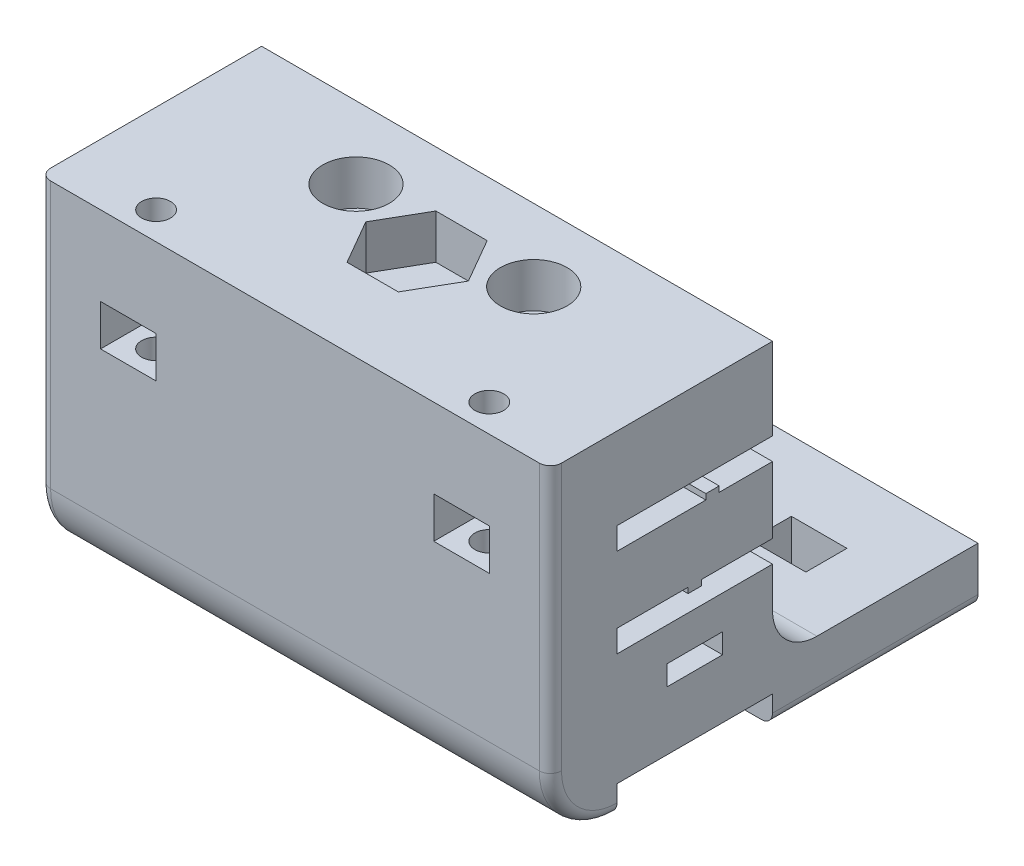
SolidWorks part; units mm, degrees
material "1060 Сплав"
ref_plane "Front" through (0, 0, 0) normal (0, 0, 1) x (1, 0, 0)
ref_plane "Top" through (0, 0, 0) normal (0, 1, 0) x (1, 0, 0)
ref_plane "Right" through (0, 0, 0) normal (1, 0, 0) x (0, 0, -1)
sketch "Эскиз1" plane through (0, 0, 0) normal (0, 0, 1) x (1, 0, 0)
  line L1 (-23, -15) -> (23, -15)
  line L2 (-23, -15) -> (-23, 15)
  line L3 (-23, 15) -> (23, 15)
  line L4 (23, -15) -> (23, 15)
  line L5 (-23, -15) -> (23, 15) construction
  line L6 (-23, 15) -> (23, -15) construction
  point P0 (0, 0)
  dimension "D1" = 30
  dimension "D2" = 46
extrude "Бобышка-Вытянуть1" add sketch "Эскиз1" along normal blind 5
sketch "Эскиз2" plane through (0, 0, 0) normal (0, 0, -1) x (-1, 0, 0)
  line L0 (23, 15) -> (23, -15) construction
  line L1 (-23, -15) -> (23, -15)
  line L2 (-23, -15) -> (-23, -10)
  line L3 (-23, -10) -> (23, -10)
  line L4 (23, -15) -> (23, -10)
  dimension "D1" = 5
extrude "Бобышка-Вытянуть2" add sketch "Эскиз2" along normal blind 33.5
sketch "Эскиз4" plane through (0, 15, 0) normal (0, 1, 0) x (1, 0, 0)
  line L0 (23, -2.5) -> (-23, -2.5) construction
  line L1 (23, -5) -> (23, 0) construction
  line L2 (-23, -5) -> (-23, 0) construction
  circle A0 centre (15, -2.5) radius 1.3
  circle A1 centre (-15, -2.5) radius 1.3
  point P10 (0, -2.5)
  dimension "D1" = 15
  dimension "D2" = 15
extrude "Вырез-Вытянуть2" cut sketch "Эскиз4" against normal blind 15
sketch "Эскиз5" plane through (0, 0, -33.5) normal (0, 0, -1) x (-1, 0, 0)
  line L0 (-23, -12.5) -> (23, -12.5) construction
  line L1 (-23, -10) -> (-23, -15) construction
  line L2 (23, -15) -> (23, -10) construction
  circle A0 centre (-20, -12.5) radius 1.3
  circle A1 centre (20, -12.5) radius 1.3
  point P10 (0, -12.5)
  dimension "D1" = 20
  dimension "D2" = 20
extrude "Вырез-Вытянуть3" cut sketch "Эскиз5" against normal blind 15
sketch "Эскиз6" plane through (0, -10, 0) normal (0, 1, 0) x (1, 0, 0)
  line L0 (-23, 23.5) -> (23, 23.5) construction
  line L1 (-23, 33.5) -> (-23, 0) construction
  line L2 (23, 33.5) -> (23, 0) construction
  line L3 (-23, 33.5) -> (23, 33.5) construction
  line L5 (-17.5, 23.5) -> (-12.5, 23.5)
  line L6 (-17.5, 23.5) -> (-17.5, 27.2)
  line L7 (-17.5, 27.2) -> (-12.5, 27.2)
  line L8 (-12.5, 23.5) -> (-12.5, 27.2)
  line L9 (12.5, 23.5) -> (17.5, 23.5)
  line L10 (12.5, 23.5) -> (12.5, 27.2)
  line L11 (12.5, 27.2) -> (17.5, 27.2)
  line L12 (17.5, 23.5) -> (17.5, 27.2)
  point P16 (0, 23.5)
  dimension "D1" = 10
  dimension "D2" = 3.7
  dimension "D3" = 5
  dimension "D4" = 3.7
  dimension "D5" = 5
  dimension "D6" = 12.5
  dimension "D7" = 12.5
extrude "Вырез-Вытянуть4" cut sketch "Эскиз6" against normal up to next
sketch "Эскиз7" plane through (0, 0, 0) normal (0, 0, -1) x (-1, 0, 0)
  line L1 (23, 15) -> (-23, 15)
  line L2 (23, 15) -> (23, -10)
  line L3 (23, -10) -> (-23, -10)
  line L4 (-23, 15) -> (-23, -10)
extrude "Бобышка-Вытянуть3" add sketch "Эскиз7" along normal blind 15
sketch "Эскиз8" plane through (0, 0, -15) normal (0, 0, -1) x (-1, 0, 0)
  line L0 (-23, 7.62) -> (23, 7.62)
  line L1 (23, -10) -> (23, 15) construction
  line L2 (-23, 15) -> (-23, -10) construction
  line L3 (-23, 5.62) -> (-23, 7.62)
  line L5 (23, 5.62) -> (-23, 5.62)
  line L6 (-23, -2.38) -> (-23, -0.38)
  line L7 (23, 5.62) -> (23, 7.62)
  line L8 (23, -2.38) -> (-23, -2.38)
  line L9 (23, -2.38) -> (23, -0.38)
  line L10 (-23, -0.38) -> (23, -0.38)
  dimension "D2" = 2
extrude "Вырез-Вытянуть5" cut sketch "Эскиз8" against normal blind 14
sketch "Эскиз10" plane through (0, 0, 5) normal (0, 0, 1) x (1, 0, 0)
  line L0 (0, 15) -> (0, -15) construction
  line L1 (23, 15) -> (-23, 15) construction
  line L2 (-23, -15) -> (23, -15) construction
  line L3 (0, 6) -> (15, 6) construction
  line L4 (-17.5, 7.85) -> (-12.5, 4.15) construction
  line L5 (17.5, 4.15) -> (12.5, 4.15)
  line L6 (17.5, 4.15) -> (17.5, 7.85)
  line L7 (17.5, 7.85) -> (12.5, 7.85)
  line L8 (12.5, 4.15) -> (12.5, 7.85)
  line L9 (17.5, 4.15) -> (12.5, 7.85) construction
  line L10 (17.5, 7.85) -> (12.5, 4.15) construction
  line L11 (-17.5, 4.15) -> (-12.5, 7.85) construction
  line L12 (-12.5, 4.15) -> (-12.5, 7.85)
  line L13 (-17.5, 7.85) -> (-12.5, 7.85)
  line L14 (-17.5, 4.15) -> (-17.5, 7.85)
  line L15 (-17.5, 4.15) -> (-12.5, 4.15)
  dimension "D1" = 15
  dimension "D2" = 5
  dimension "D3" = 3.7
  dimension "D4" = 9
extrude "Вырез-Вытянуть7" cut sketch "Эскиз10" against normal blind 5
fillet "Скругление1" radius 6 1 edges at (0, -15, 5)
fillet "Скругление2" radius 4 1 edges at (0, -10, -15)
sketch "Эскиз11" plane through (0, 0, -15) normal (0, 0, -1) x (-1, 0, 0)
  line L0 (-23, 5.62) -> (23, 5.62) construction
  line L1 (-2.5, 5.62) -> (2.5, 5.62)
  line L2 (-2.5, 5.62) -> (-2.5, -17.5157)
  line L3 (-2.5, -17.5157) -> (2.5, -17.5157)
  line L4 (2.5, 5.62) -> (2.5, -17.5157)
  line L5 (-23, 5.62) -> (23, 5.62) construction
  point P0 (0, 5.62)
  dimension "D1" = 2.5
  dimension "D2" = 2.5
extrude "Вырез-Вытянуть8" cut sketch "Эскиз11" against normal blind 14
fillet "Скругление3" radius 4 4 edges at (-2.5, -2.38, -8) (-2.5, 5.62, -8) (2.5, 5.62, -8) (2.5, -2.38, -8)
fillet "Скругление4" radius 1 6 edges at (23, -15, -17.25) (23, -13.2426, 3.2426) (-23, -15, -17.25) (-23, -13.2426, 3.2426) (23, 3, 5) (-23, 3, 5)
sketch "Эскиз12" plane through (23, 0, 0) normal (1, 0, 0) x (0, 0, -1)
  line L0 (1, 5.62) -> (9, 5.62) construction
  line L1 (1, 5.62) -> (15, 5.62) construction
  line L2 (15, 5.62) -> (10.2, 5.62) construction
  line L3 (1, -0.38) -> (15, -0.38) construction
  line L4 (9, 6.12) -> (10.2, 6.12)
  line L5 (9, 6.12) -> (9, 5.62)
  line L6 (7.4, -0.88) -> (8.6, -0.88)
  line L7 (10.2, 6.12) -> (10.2, 5.62)
  line L8 (9, 5.62) -> (10.2, 5.62)
  line L9 (8.6, -0.38) -> (7.4, -0.38)
  line L10 (7.4, -0.38) -> (7.4, -0.88)
  line L11 (8.6, -0.38) -> (8.6, -0.88)
  line L12 (15, 5.62) -> (15, -0.38) construction
  point P19 (8.6, -0.63)
  dimension "D1" = 4.8
  dimension "D2" = 1.2
  dimension "D3" = 0.5
  dimension "D4" = 0.5
  dimension "D5" = 6.4
extrude "Бобышка-Вытянуть4" add sketch "Эскиз12" against normal blind 10
sketch "Эскиз13" plane through (-23, 0, 0) normal (-1, 0, 0) x (0, 0, 1)
  line L0 (-8.6, 5.62) -> (-7.4, 5.62)
  line L1 (-8.6, 6.12) -> (-7.4, 6.12)
  line L2 (-8.6, 6.12) -> (-8.6, 5.62)
  line L3 (-10.2, -0.88) -> (-9, -0.88)
  line L4 (-7.4, 6.12) -> (-7.4, 5.62)
  line L6 (-10.2, -0.38) -> (-9, -0.38)
  line L8 (-10.2, -0.38) -> (-10.2, -0.88)
  line L9 (-9, -0.38) -> (-9, -0.88)
  line L11 (-15, -0.38) -> (-15, 5.62) construction
  dimension "D1" = 1.2
  dimension "D2" = 4.8
  dimension "D3" = 1.2
extrude "Бобышка-Вытянуть5" add sketch "Эскиз13" against normal blind 10
sketch "Эскиз14" plane through (0, -15, 0) normal (0, -1, 0) x (1, 0, 0)
  line L1 (-28.5402, -1) -> (28.5402, -1)
  line L2 (-28.5402, -1) -> (-28.5402, -15)
  line L3 (-28.5402, -15) -> (28.5402, -15)
  line L4 (28.5402, -1) -> (28.5402, -15)
  line L5 (-28.5402, -1) -> (28.5402, -15) construction
  line L6 (-28.5402, -15) -> (28.5402, -1) construction
  point P0 (0, -8)
extrude "Вырез-Вытянуть9" cut sketch "Эскиз14" against normal blind 2.5
fillet "Скругление5" radius 4 2 edges at (2.5, -12.5, -8) (-2.5, -12.5, -8)
sketch "Эскиз15" plane through (0, -12.5, 0) normal (0, -1, 0) x (1, 0, 0)
  line L0 (-23, -8) -> (23, -8) construction
  line L1 (-23, -1) -> (-23, -15) construction
  line L2 (23, -15) -> (23, -1) construction
  circle A2 centre (-19, -8) radius 1.3
  circle A3 centre (19, -8) radius 1.3
  dimension "D1" = 4
  dimension "D2" = 4
extrude "Вырез-Вытянуть10" cut sketch "Эскиз15" against normal blind 8
sketch "Эскиз16" plane through (-23, 0, 0) normal (-1, 0, 0) x (0, 0, 1)
  line L0 (-8, -12.5) -> (-8, -6.3) construction
  line L1 (-10.5, -5.4) -> (-5.5, -5.4)
  line L2 (-10.5, -5.4) -> (-10.5, -7.2)
  line L3 (-10.5, -7.2) -> (-5.5, -7.2)
  line L4 (-5.5, -5.4) -> (-5.5, -7.2)
  line L5 (-10.5, -5.4) -> (-5.5, -7.2) construction
  line L6 (-10.5, -7.2) -> (-5.5, -5.4) construction
  line L7 (-1, -12.5) -> (-15, -12.5) construction
  point P0 (-8, -6.3)
  dimension "D1" = 5
  dimension "D2" = 1.8
  dimension "D3" = 6.2
extrude "Вырез-Вытянуть11" cut sketch "Эскиз16" against normal blind 7
sketch "Эскиз17" plane through (23, 0, 0) normal (1, 0, 0) x (0, 0, -1)
  line L0 (8, -12.5) -> (8, -6.3) construction
  line L1 (15, -12.5) -> (1, -12.5) construction
  line L3 (5.5, -5.4) -> (10.5, -5.4)
  line L4 (5.5, -5.4) -> (5.5, -7.2)
  line L5 (5.5, -7.2) -> (10.5, -7.2)
  line L6 (10.5, -5.4) -> (10.5, -7.2)
  line L7 (5.5, -5.4) -> (10.5, -7.2) construction
  line L8 (5.5, -7.2) -> (10.5, -5.4) construction
  dimension "D1" = 6.2
  dimension "D2" = 1.8
  dimension "D3" = 5
extrude "Вырез-Вытянуть12" cut sketch "Эскиз17" against normal blind 7
sketch "Эскиз18" plane through (0, 15, 0) normal (0, 1, 0) x (1, 0, 0)
  line L0 (0, 15) -> (0, -5) construction
  line L1 (-23, 15) -> (23, 15) construction
  line L2 (22, -5) -> (-22, -5) construction
  line L3 (0, 8.5) -> (8, 8.5) construction
  line L5 (4.6188, 6) -> (2.3094, 10)
  line L6 (2.3094, 10) -> (-2.3094, 10)
  line L7 (-2.3094, 10) -> (-4.6188, 6)
  line L8 (-4.6188, 6) -> (-2.3094, 2)
  line L9 (-2.3094, 2) -> (2.3094, 2)
  line L10 (2.3094, 2) -> (4.6188, 6)
  circle A0 centre (8, 8.5) radius 3
  circle A1 centre (-8, 8.5) radius 3
  circle A2 centre (0, 6) radius 4 construction
  dimension "D2" = 13.5
  dimension "D1" = 8
  dimension "D3" = 11
extrude "Вырез-Вытянуть13" cut sketch "Эскиз18" against normal blind 4
